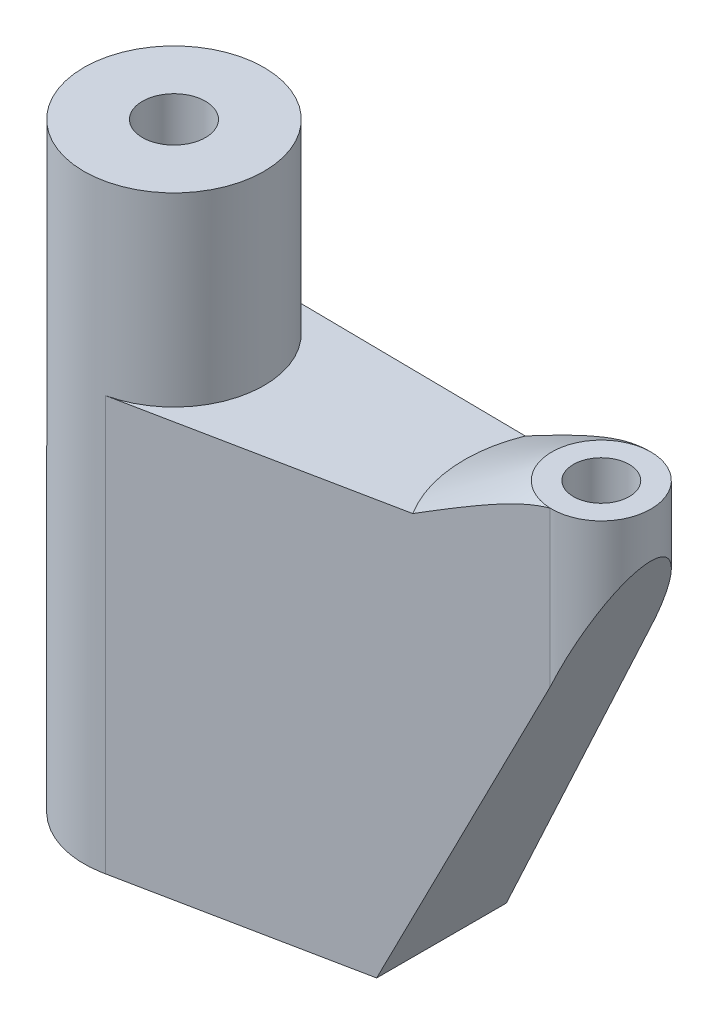
SolidWorks part; units mm, degrees
ref_plane "Front Plane" through (0, 0, 0) normal (0, 0, 1) x (1, 0, 0)
ref_plane "Top Plane" through (0, 0, 0) normal (0, 1, 0) x (1, 0, 0)
ref_plane "Right Plane" through (0, 0, 0) normal (1, 0, 0) x (0, 0, -1)
sketch "Sketch1" plane through (0, 0, 0) normal (0, 1, 0) x (1, 0, 0)
  line L5 (-5, 5) -> (5, -5) construction
  line L6 (-5, -5) -> (5, 5) construction
  circle A0 centre (0, 0) radius 1.75
  circle A5 centre (0, 0) radius 5
  point P0 (0, 0)
  dimension "D2" = 3.5
  dimension "D4" = 10
  dimension "D1" = 10
  dimension "D3" = 10
extrude "Boss-Extrude1" add sketch "Sketch1" along normal blind 33.3
sketch "Sketch2" plane through (0, 0, 0) normal (0, 1, 0) x (1, 0, 0)
  circle A0 centre (21.73, 2) radius 2.75
  dimension "D1" = 5.5
  dimension "D2" = 21.73
  dimension "D3" = 2
extrude "Boss-Extrude2" add sketch "Sketch2" along normal blind 25.8 separate body
sketch "Sketch4" plane through (0, 0, 0) normal (0, -1, 0) x (1, 0, 0)
  line L0 (21.6378, 0.7485) -> (0.8914, 4.9199)
  line L1 (0.8914, 4.9199) -> (2.6702, 0)
  line L2 (21.6378, 0.7485) -> (21.6378, -4.7485)
  line L3 (21.6378, -4.7485) -> (0.0144, -5)
  line L4 (0.0144, -5) -> (2.6702, 0)
  circle A0 centre (21.73, -2) radius 2.75 construction
  circle A1 centre (0, 0) radius 5 construction
extrude "Boss-Extrude3" add sketch "Sketch4" against normal blind 23
sketch "Sketch3" plane through (0, 25.8, 0) normal (0, 1, 0) x (1, 0, 0)
  circle A0 centre (21.73, 2) radius 1.55
  dimension "D1" = 3.1
extrude "Cut-Extrude1" cut sketch "Sketch3" against normal blind 3
sketch "Sketch5" plane through (0, 0, 0) normal (0, 0, 1) x (1, 0, 0)
  line L0 (24.48, 23.3) -> (12.5902, -2.1978)
  line L1 (24.48, 0) -> (24.48, 25.8) construction
  line L4 (24.48, 25.8) -> (18.98, 25.8) construction
  line L7 (24.48, 23.3) -> (24.48, 11.7821)
  line L11 (24.48, 0) -> (24.48, 11.7821)
  line L13 (12.5902, -2.1978) -> (24.48, 0)
  point P5 (10.4132, -1.5645)
  point P7 (24.48, 0)
  dimension "D1" = 2.5
  dimension "D2" = 25
extrude "Cut-Extrude2" cut sketch "Sketch5" against normal through all both and the other way through all
chamfer "Chamfer3" distance 2.8 angle 60 1 edges at (18.98, 23, -2) first distance on face at (21.6839, 21.6262, -2)
